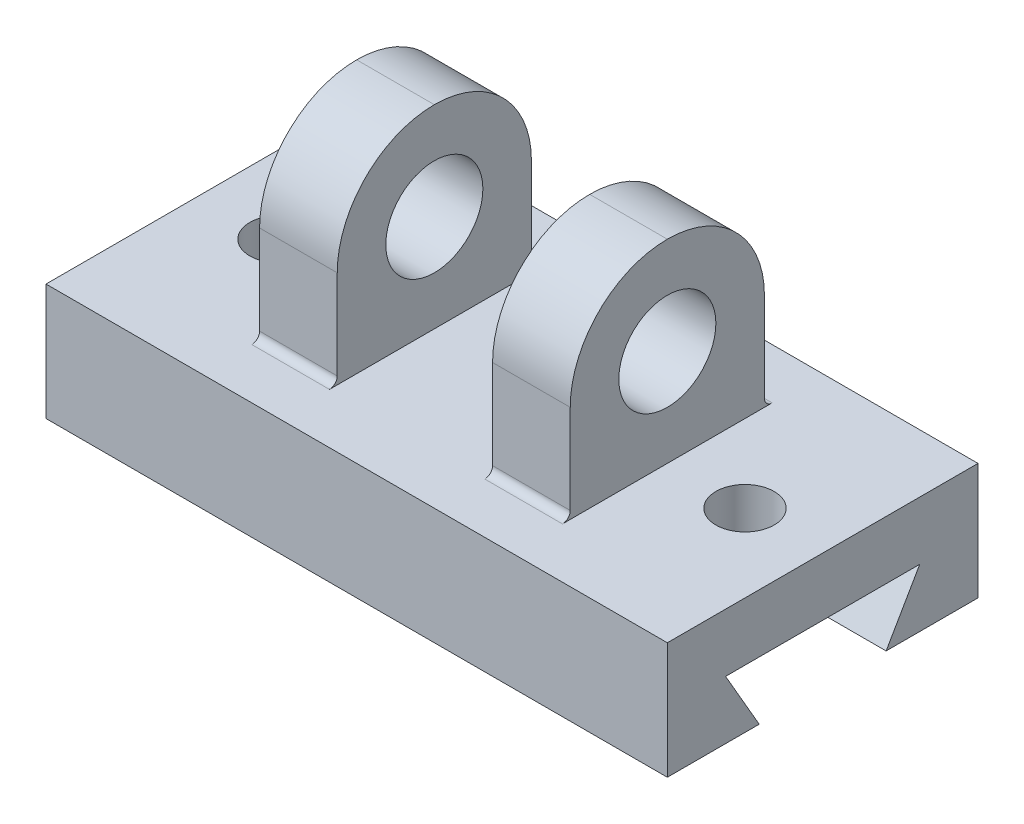
SolidWorks part; units mm, degrees
ref_plane "Front Plane" through (0, 0, 0) normal (0, 0, 1) x (1, 0, 0)
ref_plane "Top Plane" through (0, 0, 0) normal (0, 1, 0) x (1, 0, 0)
ref_plane "Right Plane" through (0, 0, 0) normal (1, 0, 0) x (0, 0, -1)
sketch "Sketch1" plane through (0, 0, 0) normal (1, 0, 0) x (0, 0, -1)
  line L0 (0, 0) -> (-80, 0)
  line L1 (-80, 0) -> (-80, -30)
  line L2 (-80, -30) -> (-56.3397, -30)
  line L3 (-56.3397, -30) -> (-65, -15)
  line L4 (-65, -15) -> (-15, -15)
  line L5 (-15, -15) -> (-23.6603, -30)
  line L6 (-23.6603, -30) -> (0, -30)
  line L7 (0, -30) -> (0, 0)
  point P7 (-80, -15)
  dimension "D1" = 80
  dimension "D2" = 15
  dimension "D3" = 30
  dimension "D4" = 15
  dimension "D5" = 30
  dimension "D6" = 60
  dimension "D7" = 60
  dimension "D8" = 15
extrude "Boss-Extrude2" add sketch "Sketch1" along normal blind 80
sketch "Sketch3" plane through (0, 0, 0) normal (0, 1, 0) x (1, 0, 0)
  line L0 (40, -15) -> (40, -65)
  line L1 (40, -65) -> (20, -65)
  line L2 (20, -65) -> (20, -15)
  line L3 (20, -15) -> (40, -15)
  line L4 (80, 0) -> (80, -80) construction
  point P6 (40, -40)
  point P7 (80, -40)
  dimension "D1" = 40
  dimension "D2" = 20
  dimension "D3" = 50
  dimension "D4" = 0
extrude "Boss-Extrude3" add sketch "Sketch3" along normal blind 50
fillet "Fillet3" radius 25 2 edges at (30, 50, 65) (30, 50, 15)
sketch "Sketch8" plane through (40, 0, 0) normal (1, 0, 0) x (0, 0, -1)
  circle A2 centre (-40, 25) radius 12.5
extrude "Cut-Extrude1" cut sketch "Sketch8" against normal blind 50
sketch "Sketch9" plane through (0, 0, 0) normal (0, 1, 0) x (1, 0, 0)
  line L0 (80, 0) -> (0, 0) construction
  line L1 (40, -65) -> (40, -15) construction
  circle A0 centre (60, -40) radius 7.5
  dimension "D1" = 40
  dimension "D2" = 20
extrude "Cut-Extrude3" cut sketch "Sketch9" against normal blind 50
fillet "Fillet4" radius 2 1 edges at (30, 0, 65)
fillet "Fillet5" radius 2 1 edges at (30, 0, 15)
mirror "Mirror14" about plane through (0, 0, 0) normal (1, 0, 0) of "Fillet5", "Fillet4", "Cut-Extrude3", "Cut-Extrude1", "Fillet3", "Boss-Extrude3", "Boss-Extrude2"
